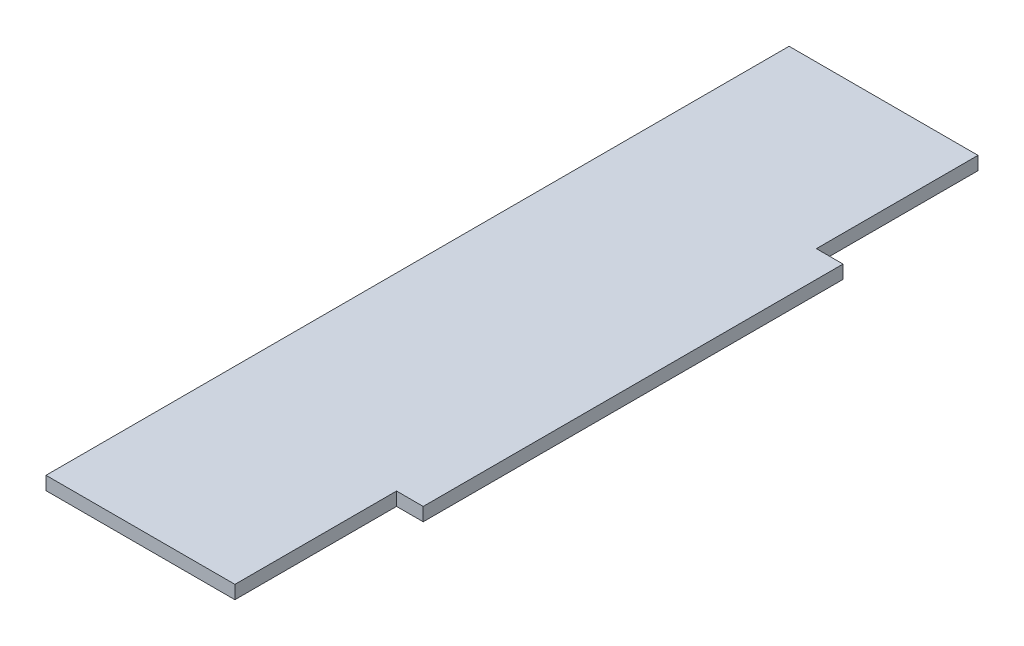
SolidWorks part; units mm, degrees
ref_plane "Front Plane" through (0, 0, 0) normal (0, 0, 1) x (1, 0, 0)
ref_plane "Top Plane" through (0, 0, 0) normal (0, 1, 0) x (1, 0, 0)
ref_plane "Right Plane" through (0, 0, 0) normal (1, 0, 0) x (0, 0, -1)
sketch "Sketch1" plane through (0, 0, 0) normal (0, 1, 0) x (1, 0, 0)
  line L0 (-22.5, 38.5) -> (22.5, 38.5)
  line L1 (22.5, 38.5) -> (22.5, 0)
  line L2 (22.5, 0) -> (28.85, 0)
  line L3 (28.85, 0) -> (28.85, -100)
  line L4 (28.85, -100) -> (22.5, -100)
  line L5 (22.5, -100) -> (22.5, -138.5)
  line L6 (22.5, -138.5) -> (-22.5, -138.5)
  line L7 (-22.5, -138.5) -> (-22.5, -100)
  line L8 (-22.5, -100) -> (-28.85, -100)
  line L9 (-28.85, -100) -> (-28.85, 0)
  line L10 (-28.85, 0) -> (-22.5, 0)
  line L11 (-22.5, 0) -> (-22.5, 38.5)
  line L12 (-22.5, 0) -> (-22.5, -100) construction
  point P11 (0, 38.5)
  point P14 (-28.85, -50)
  dimension "D1" = 6.35
  dimension "D2" = 100
  dimension "D3" = 45
  dimension "D4" = 177
extrude "Boss-Extrude1" add sketch "Sketch1" along normal blind 3.175 contours L11 L12 L7 L6 L5 L4 L3 L2 L1 L0 region at (1.8958, 0, 50)
equation "\"length\"= 177mm"
equation "\"w_mach\"= 45mm"
equation "\"w_tab\"= 100mm"
equation "\"t_wood\"= 0.125in"
equation "\"t_side\"= 0.25in"
equation "\"D1@Sketch1\"=\"t_side\""
equation "\"D2@Sketch1\"=\"w_tab\""
equation "\"D3@Sketch1\"=\"w_mach\""
equation "\"D4@Sketch1\"=\"length\""
equation "\"D1@Boss-Extrude1\"=\"t_wood\""
